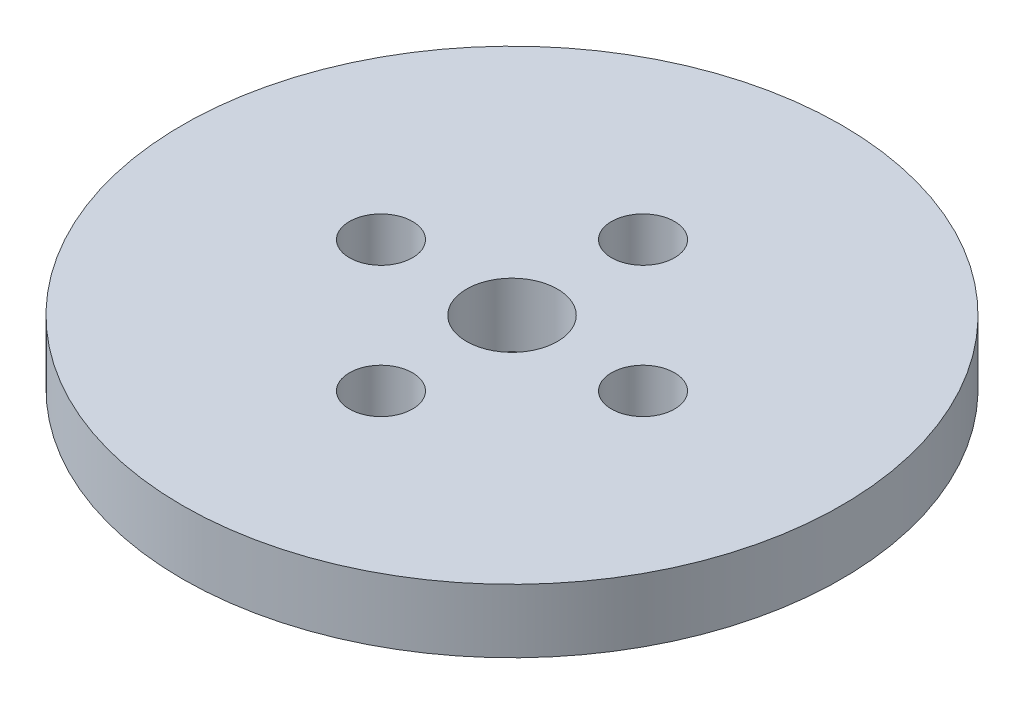
SolidWorks part; units mm, degrees
ref_plane "Front Plane" through (0, 0, 0) normal (0, 0, 1) x (1, 0, 0)
ref_plane "Top Plane" through (0, 0, 0) normal (0, 1, 0) x (1, 0, 0)
ref_plane "Right Plane" through (0, 0, 0) normal (1, 0, 0) x (0, 0, -1)
sketch "Sketch1" plane through (0, 0, 0) normal (0, 1, 0) x (1, 0, 0)
  circle A0 centre (0, 0) radius 72.5
  dimension "FLANGE_OD" = 145
extrude "Boss-Extrude1" add sketch "Sketch1" along normal blind 14
sketch "Sketch2" plane through (0, 0, 0) normal (0, 1, 0) x (1, 0, 0)
  circle A0 centre (0, 0) radius 10
  dimension "BORE_D" = 20
extrude "Cut-Extrude1" cut sketch "Sketch2" along normal through all
sketch "Sketch3" plane through (0, 14, 0) normal (0, 1, 0) x (1, 0, 0)
  circle A0 centre (0, 0) radius 28.8253 construction
  circle A1 centre (-28.8253, 0) radius 6.9316
  dimension "BOLT_D" = 13.8631
  dimension "BOLT_PCD" = 57.6506
extrude "Cut-Extrude2" cut sketch "Sketch3" against normal blind 12.172
pattern_circular "CirPattern1" count 4 over 360 about axis through (0, 0, 0) along (0, 1, 0) of "Cut-Extrude2"
